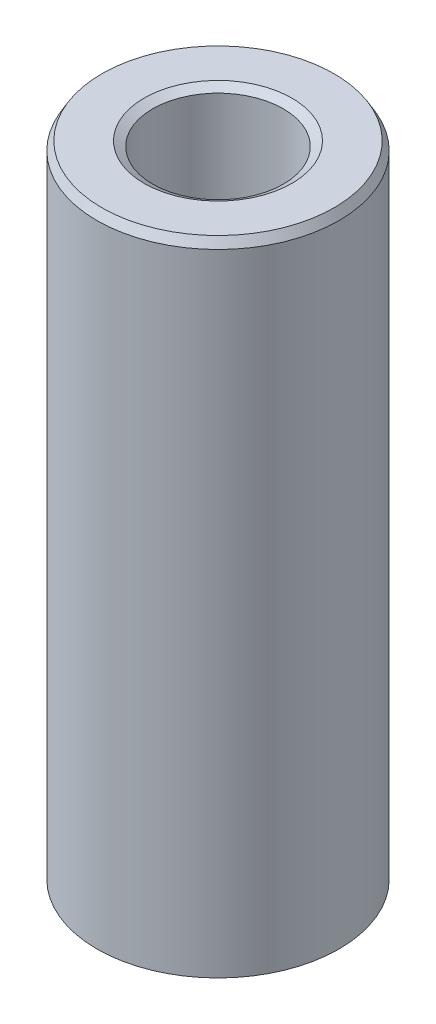
SolidWorks part; units mm, degrees
ref_plane "Front Plane" through (0, 0, 0) normal (0, 0, 1) x (1, 0, 0)
ref_plane "Top Plane" through (0, 0, 0) normal (0, 1, 0) x (1, 0, 0)
ref_plane "Right Plane" through (0, 0, 0) normal (1, 0, 0) x (0, 0, -1)
sketch "Sketch1" plane through (0, 0, 0) normal (0, 1, 0) x (1, 0, 0)
  circle A0 centre (0, 0) radius 35
  dimension "SLEEVE_OD" = 70
extrude "Boss-Extrude1" add sketch "Sketch1" along normal blind 186.2929
sketch "Sketch2" plane through (0, 0, 0) normal (0, 1, 0) x (1, 0, 0)
  circle A0 centre (0, 0) radius 18.882
  dimension "BORE_D" = 37.764
extrude "Cut-Extrude1" cut sketch "Sketch2" along normal through all
chamfer "Chamfer1" distance 2.4843 angle 30 4 edges at (0, 186.2929, 18.882) (0, 0, 18.882) (0, 0, 35) (0, 186.2929, 35) first distance on face at (0, 186.2929, 18.882) first distance on face at (0, 0, 18.882) first distance on face at (0, 186.2929, 35)
